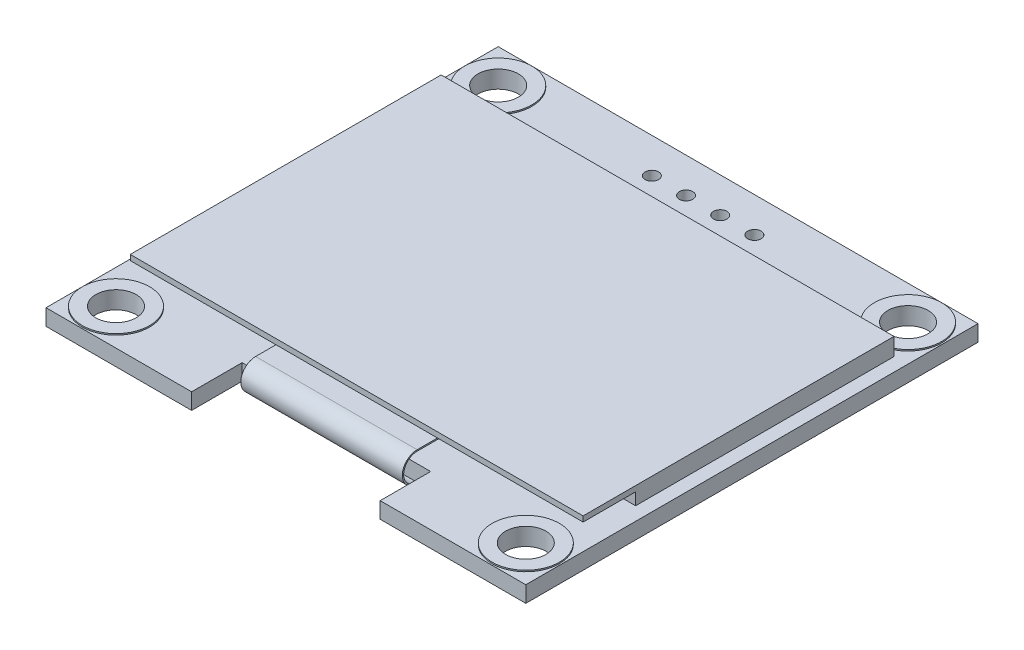
SolidWorks part; units mm, degrees
ref_plane "Alzado" through (0, 0, 0) normal (0, 0, 1) x (1, 0, 0)
ref_plane "Planta" through (0, 0, 0) normal (0, 1, 0) x (1, 0, 0)
ref_plane "Vista lateral" through (0, 0, 0) normal (1, 0, 0) x (0, 0, -1)
sketch "Croquis1" plane through (0, 0, 0) normal (0, 1, 0) x (1, 0, 0)
  line L0 (-7.005, 0) -> (7.005, 0)
  line L1 (-50, 0) -> (50, 0) construction
  line L2 (0, 29.85) -> (0, 0) construction
  line L3 (7.005, 0) -> (7.005, -3.75)
  line L4 (7.005, -3.75) -> (17.825, -3.75)
  line L5 (17.825, -3.75) -> (17.825, 29.85)
  line L6 (17.825, 29.85) -> (-17.825, 29.85)
  line L7 (-17.825, 29.85) -> (-17.825, -3.75)
  line L8 (-17.825, -3.75) -> (-7.005, -3.75)
  line L9 (-7.005, -3.75) -> (-7.005, 0)
  line L10 (-15.225, 27.25) -> (-15.225, -1.15) construction
  line L11 (-15.225, -1.15) -> (15.225, -1.15) construction
  line L12 (15.225, -1.15) -> (15.225, 27.25) construction
  line L13 (15.225, 27.25) -> (-15.225, 27.25) construction
  line L14 (-1.27, 26.75) -> (1.27, 26.75) construction
  circle A0 centre (-15.225, 27.25) radius 2.5
  circle A1 centre (15.225, 27.25) radius 2.5
  circle A2 centre (-15.225, -1.15) radius 2.5
  circle A3 centre (15.225, -1.15) radius 2.5
  circle A4 centre (-1.27, 27.25) radius 0.5
  circle A5 centre (-3.81, 27.25) radius 0.5
  circle A6 centre (1.27, 27.25) radius 0.5
  circle A7 centre (3.81, 27.25) radius 0.5
  point P6 (0, 0)
  point P32 (0, 26.75)
  dimension "D5" = 5
  dimension "D10" = 1
  dimension "D1" = 10.82
  dimension "D2" = 35.65
  dimension "D3" = 33.6
  dimension "D4" = 3.75
  dimension "D6" = 2.6
  dimension "D7" = 2.6
  dimension "D8" = 2.6
  dimension "D9" = 2.6
  dimension "D11" = 2.54
  dimension "D12" = 2.54
  dimension "D13" = 2.54
extrude "Saliente-Extruir1" add sketch "Croquis1" along normal blind 1.2 separate body
sketch "Croquis2" plane through (0, 1.2, 0) normal (0, 1, 0) x (1, 0, 0)
  circle A0 centre (-15.225, 27.25) radius 2.5
  circle A1 centre (-15.225, 27.25) radius 1.5
  circle A2 centre (15.225, 27.25) radius 2.5
  circle A3 centre (-15.225, -1.15) radius 2.5
  circle A4 centre (15.225, -1.15) radius 2.5
  circle A5 centre (15.225, 27.25) radius 1.5
  circle A6 centre (15.225, -1.15) radius 1.5
  circle A7 centre (-15.225, -1.15) radius 1.5
  dimension "D1" = 5
  dimension "D2" = 3
extrude "Saliente-Extruir2" add sketch "Croquis2" along direction (0, 1, 0) on the side against the normal up to surface (1.2 mm away) and the other way blind 0.1 separate body up to face at (0, 0, -5.5875)
sketch "Croquis3" plane through (0, 0, 0) normal (1, 0, 0) x (0, 0, -1)
  line L0 (24.61, 1.2) -> (24.61, 2.5)
  line L1 (-3.75, 1.2) -> (29.85, 1.2) construction
  line L2 (24.61, 2.5) -> (1.51, 2.5)
  line L3 (1.51, 2.5) -> (1.51, 2.1)
  line L4 (1.51, 2.1) -> (5.41, 2.1)
  line L5 (5.41, 2.1) -> (5.41, 1.2)
  line L6 (5.41, 1.2) -> (24.61, 1.2)
  line L7 (-3.75, 1.2) -> (-3.75, 0) construction
  dimension "D1" = 1.3
  dimension "D2" = 0.9
  dimension "D3" = 23.1
  dimension "D4" = 5.26
  dimension "D5" = 3.9
extrude "Saliente-Extruir3" add sketch "Croquis3" along normal blind 16.825 and the other way blind 16.825 separate body
sketch "Croquis4" plane through (0, 0, 0) normal (0, -1, 0) x (1, 0, 0)
  line L0 (11, -7) -> (-11, -7)
  line L1 (-11, -7) -> (-11, -4)
  line L2 (-11, -4) -> (-6, -2.5585)
  line L3 (-6, -2.5585) -> (-6, 0)
  line L4 (11, -7) -> (11, -4)
  line L5 (11, -4) -> (6, -2.5585)
  line L6 (6, -2.5585) -> (6, 0)
  line L7 (6, 0) -> (-6, 0)
  line L8 (0, -7) -> (0, 0) construction
  line L9 (-7.005, 0) -> (7.005, 0) construction
  point P11 (0, 0)
  point P14 (0, 0)
  dimension "D1" = 22
  dimension "D2" = 12
  dimension "D3" = 3
  dimension "D4" = 2.5585
  dimension "D5" = 7
extrude "Saliente-Extruir4" add sketch "Croquis4" along normal blind 0.1 separate body
sketch "Croquis5" plane through (0, 0, 0) normal (1, 0, 0) x (0, 0, -1)
  line L0 (1.51, 2.1) -> (3.0684, 2.1)
  line L1 (1.51, 2.1) -> (5.41, 2.1) construction
  line L2 (1.51, 2.1) -> (0, 2.1)
  line L3 (0, 50) -> (0, -50) construction
  line L4 (2.5585, -0.1) -> (0, -0.1) construction
  line L5 (1.51, 2) -> (3.0684, 2)
  line L6 (1.51, 2) -> (0, 2)
  line L7 (3.0684, 2.1) -> (3.0684, 2)
  line L8 (0, 0) -> (0, -0.1)
  arc A0 (0, 2.1) -> (0, -0.1) centre (0, 1) ccw
  arc A1 (0, 2) -> (0, 0) centre (0, 1) ccw
  dimension "D1" = 0.1
extrude "Saliente-Extruir5" add sketch "Croquis5" along normal up to vertex (6 mm away) and the other way up to vertex (6 mm away) up to point (6, -0.1, 0) other way up to point (-6, -0.1, 0)
sketch "Líneas de pliegue1" [suppressed] plane through (0, 0, 0) normal (0, 1, 0) x (1, 0, 0)
sketch "Cuadro delimitador1" [suppressed] plane through (0, 0, 0) normal (0, 1, 0) x (1, 0, 0)
